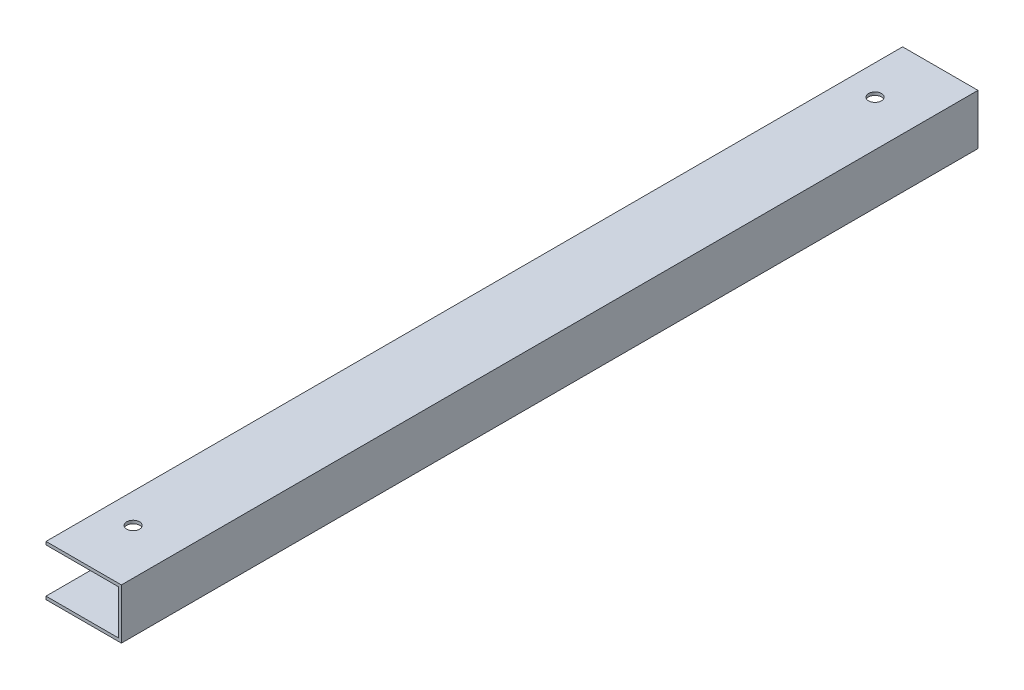
SolidWorks part; units mm, degrees
material "AISI 1020 Acero laminado en frío"
ref_plane "Alzado" through (0, 0, 0) normal (0, 0, 1) x (1, 0, 0)
ref_plane "Planta" through (0, 0, 0) normal (0, 1, 0) x (1, 0, 0)
ref_plane "Vista lateral" through (0, 0, 0) normal (1, 0, 0) x (0, 0, -1)
sketch "Croquis2" plane through (0, 0, 0) normal (0, 0, 1) x (1, 0, 0)
  line L1 (38.1, -25.5) -> (-38.1, -25.5)
  line L2 (38.1, -25.5) -> (38.1, 25.5)
  line L3 (38.1, 25.5) -> (-38.1, 25.5)
  line L4 (-38.1, -25.5) -> (-38.1, 25.5)
  line L5 (38.1, -25.5) -> (-38.1, 25.5) construction
  line L6 (38.1, 25.5) -> (-38.1, -25.5) construction
  point P0 (0, 0)
  point P6 (0, 25.5)
  dimension "D1" = 51
  dimension "D2" = 76.2
extrude "Saliente-Extruir1" add sketch "Croquis2" along normal mid plane 866
sketch "Croquis6" plane through (0, 0, 433) normal (0, 0, 1) x (1, 0, 0)
  line L4 (-38.1, 25.5) -> (-38.1, -25.5)
  line L5 (-38.1, -25.5) -> (38.1, -25.5)
  line L6 (38.1, -25.5) -> (38.1, 25.5)
  line L7 (38.1, 25.5) -> (-38.1, 25.5)
  line L8 (-38.1, 25.5) -> (-38.1, -25.5)
  line L9 (-38.1, -25.5) -> (38.1, -25.5)
  line L10 (38.1, -25.5) -> (38.1, 25.5)
  line L11 (38.1, 25.5) -> (-38.1, 25.5)
  line L16 (-35, 22.4) -> (-35, -22.4)
  line L17 (-35, -22.4) -> (35, -22.4)
  line L18 (35, -22.4) -> (35, 22.4)
  line L19 (35, 22.4) -> (-35, 22.4)
  line L20 (-35, 22.4) -> (-35, -22.4)
  line L21 (-35, -22.4) -> (35, -22.4)
  line L22 (35, -22.4) -> (35, 22.4)
  line L23 (35, 22.4) -> (-35, 22.4)
  dimension "D1" = 0
  dimension "D2" = 3.1
extrude "Cortar-Extruir1" cut sketch "Croquis6" against normal blind 900 contours L22 L23 L20 L21 region at (0, 0, 433)
sketch "Croquis7" plane through (-38.1, 0, 0) normal (-1, 0, 0) x (0, 0, 1)
  line L0 (-433, 25.5) -> (-433, -25.5) construction
  line L1 (433, -22.4) -> (-433, -22.4)
  line L2 (433, -22.4) -> (433, 22.4)
  line L3 (433, 22.4) -> (-433, 22.4)
  line L4 (-433, -22.4) -> (-433, 22.4)
  line L5 (433, -22.4) -> (-433, 22.4) construction
  line L6 (433, 22.4) -> (-433, -22.4) construction
  line L7 (433, -25.5) -> (-433, -25.5) construction
  point P0 (0, 0)
  dimension "D1" = 3.1
extrude "Cortar-Extruir2" cut sketch "Croquis7" against normal blind 20
sketch "Croquis8" plane through (0, 25.5, 0) normal (0, 1, 0) x (1, 0, 0)
  line L0 (-121.5247, 0) -> (93.3442, 0) construction
  line L1 (0, 497.4221) -> (0, -494.6167) construction
  circle A0 centre (-8, 375) radius 6.5
  circle A1 centre (-8, -375) radius 6.5
  dimension "D1" = 13
  dimension "D2" = 375
  dimension "D3" = 8
extrude "Cortar-Extruir3" cut sketch "Croquis8" against normal blind 80
